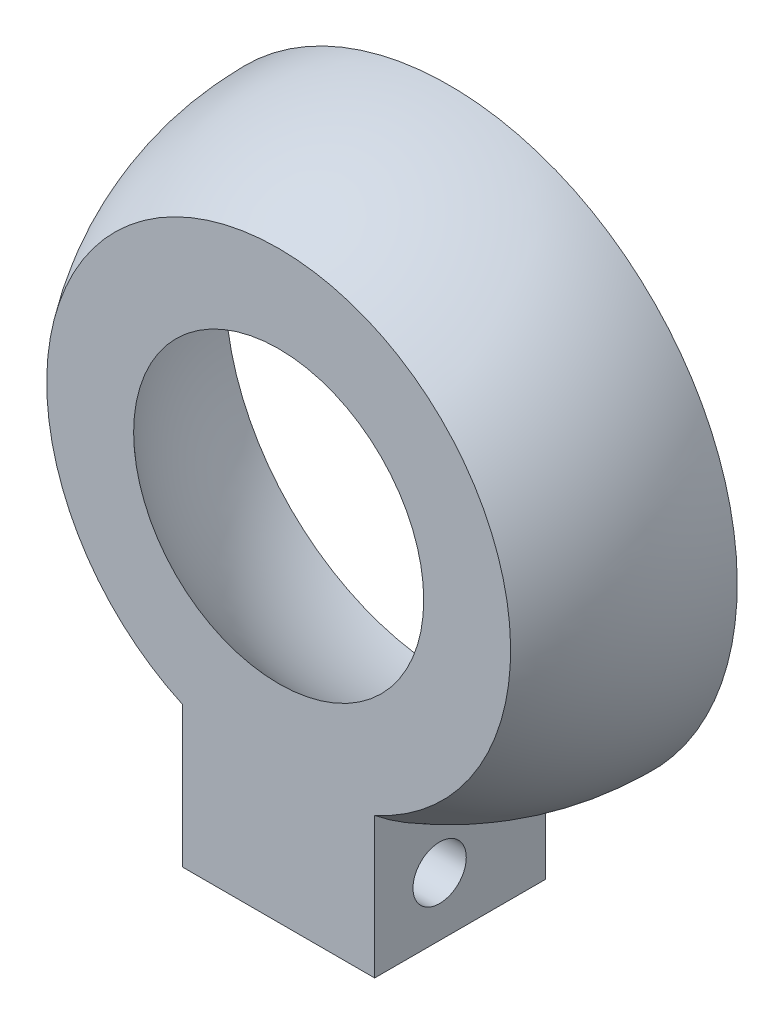
SolidWorks part; units mm, degrees
ref_plane "Front Plane" through (0, 0, 0) normal (0, 0, 1) x (1, 0, 0)
ref_plane "Top Plane" through (0, 0, 0) normal (0, 1, 0) x (1, 0, 0)
ref_plane "Right Plane" through (0, 0, 0) normal (1, 0, 0) x (0, 0, -1)
sketch "Sketch4" plane through (0, 60.25, 0) normal (0, 1, 0) x (1, 0, 0)
  line L0 (-103.35, -1.5487) -> (10.75, -1.5487) construction
  line L1 (-7.75, 16.4513) -> (1.25, 16.4513)
  line L2 (-7.75, 16.4513) -> (-7.75, 0.4513)
  line L3 (-7.75, 0.4513) -> (1.25, 0.4513)
  line L4 (1.25, 16.4513) -> (1.25, 0.4513)
  line L5 (1.25, 6) -> (1.25, 1.5) construction
  line L6 (-5.75, 4.9513) -> (-7.75, 4.9513) construction
  line L7 (-3.25, 2.4513) -> (-3.25, 0.4513) construction
  line L8 (-3.25, 9.4513) -> (-3.25, 7.4513) construction
  line L9 (-0.75, 4.9513) -> (1.25, 4.9513) construction
  line L11 (-3.25, 14.4513) -> (-3.25, 16.4513) construction
  line L12 (-38.5, -1.5487) -> (38.5, -1.5487) construction
  line L13 (-7.75, 16.4513) -> (1.25, 16.4513)
  line L14 (-7.75, 16.4513) -> (-7.75, 8.4513)
  line L15 (-7.75, 8.4513) -> (1.25, 8.4513)
  line L16 (1.25, 16.4513) -> (1.25, 8.4513)
  line L17 (1.25, 8.4513) -> (-7.75, 8.4513)
  line L18 (1.25, 8.4513) -> (1.25, 0.4513)
  line L19 (1.25, 0.4513) -> (-7.75, 0.4513)
  line L20 (-7.75, 8.4513) -> (-7.75, 0.4513)
  circle A0 centre (-3.25, 4.9513) radius 2.5 construction
  circle A1 centre (-3.25, 11.9513) radius 1.25
  circle A2 centre (-3.25, 8.4513) radius 10 construction
  circle A4 centre (-3.25, 11.9513) radius 2.5 construction
  point P26 (-3.25, 8.4513)
  circle M37 centre (-3.25, 11.9513) radius 1.25
  dimension "D1" = 20
  dimension "D2" = 5
  dimension "D3" = 2
extrude "BaseBoss" add sketch "Sketch4" along normal blind 3 contours A0 | A4 | L15 L2 L3 L4 M37 region at (-3.25, 60.25, -4.4513)
ref_plane "RevolveSketchPlane" through (-3.25, 0, 0) normal (-1, 0, 0) x (0, 0, 1)
sketch "Sketch5" plane through (-3.25, 0, 0) normal (-1, 0, 0) x (0, 0, 1)
  line L0 (-8.4513, 63.25) -> (-8.4513, 66.25)
  line L2 (-8.4513, 63.25) -> (-0.4513, 63.25) construction
  line L3 (-8.4513, 63.25) -> (-0.4513, 63.25) construction
  line L4 (-0.4513, 76.75) -> (-8.4513, 76.75) construction
  line L5 (-0.4513, 63.25) -> (-0.4513, 60.25) construction
  line L7 (-0.4513, 63.25) -> (-0.4513, 60.25) construction
  line L8 (-0.4513, 65.8757) -> (-0.4513, 69.9493)
  arc A0 (-8.4513, 63.25) -> (-0.4513, 65.8757) centre (-8.4513, 76.75) ccw
  arc A1 (-8.4513, 66.25) -> (-0.4513, 69.9493) centre (-8.4513, 76.75) ccw
  dimension "D1" = 21
  dimension "D2" = 3
revolve "CoverRevolve" add sketch "Sketch5" angle 360 about L4
extrude "Boss-Extrude3" add sketch "Sketch4<5>" along normal up to surface (7.0132 mm away) contours L15 L2 L3 L4 M37 region at (-3.25, 60.25, -4.4513) up to face at (7.25, 76.75, -8.4513)
sketch "Sketch4<5>" plane through (0, 60.25, 0) normal (0, 1, 0) x (1, 0, 0) same geometry as "Sketch4"
ref_plane "BasePlane" through (0, 63.25, 0) normal (0, -1, 0) x (-1, 0, 0)
sketch "Sketch7" plane through (1.25, 0, 0) normal (1, 0, 0) x (0, 0, -1)
  circle A0 centre (3.4967, 63) radius 1.25 construction
  circle A1 centre (3.4967, 63) radius 1.25
extrude "Cut-Extrude2" cut sketch "Sketch7" against normal up to next
equation "\"D1@Sketch5\"=2*(10+.5)"
